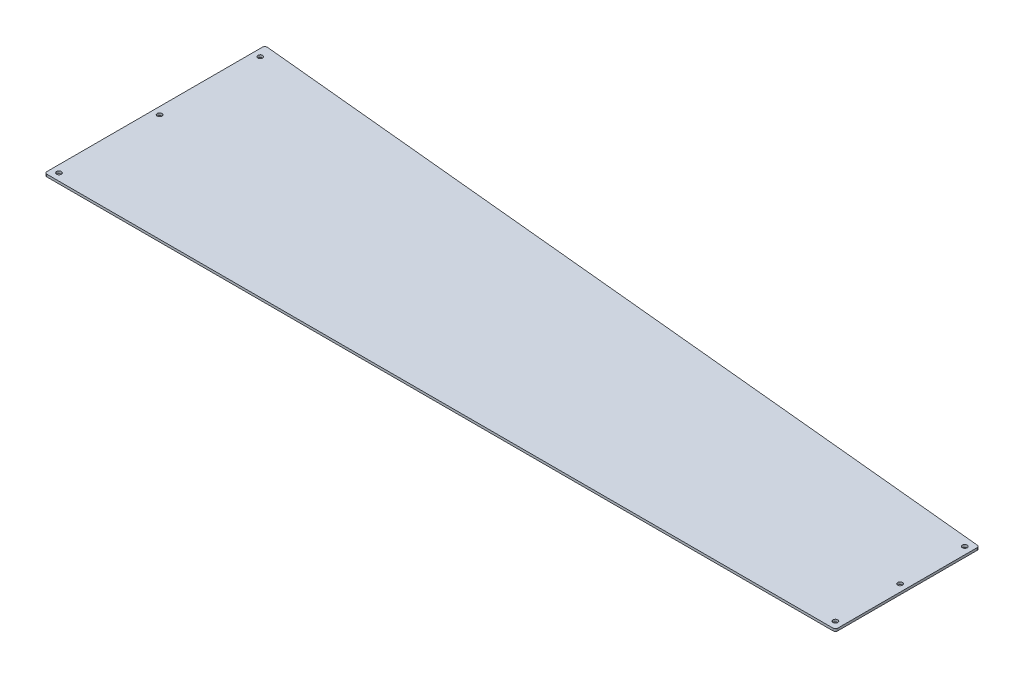
SolidWorks part; units mm, degrees
material "PC High Viscosity"
ref_plane "Front Plane" through (0, 0, 0) normal (0, 0, 1) x (1, 0, 0)
ref_plane "Top Plane" through (0, 0, 0) normal (0, 1, 0) x (1, 0, 0)
ref_plane "Right Plane" through (0, 0, 0) normal (1, 0, 0) x (0, 0, -1)
sketch "Sketch1" plane through (0, 0, 0) normal (0, 1, 0) x (1, 0, 0)
  line L0 (-634.1645, 176.7974) -> (413.5855, 75.1974)
  line L2 (-634.1645, 176.7974) -> (-634.1645, -115.3026)
  line L3 (-634.1645, -115.3026) -> (413.5855, -115.3026)
  line L4 (413.5855, 75.1974) -> (413.5855, -115.3026)
  line L5 (-634.1645, 176.7974) -> (413.5855, -115.3026) construction
  line L6 (-634.1645, -115.3026) -> (413.5855, 75.1974) construction
  point P0 (0, 0)
  dimension "D1" = 292.1
  dimension "D2" = 1047.75
  dimension "D3" = 190.5
extrude "Boss-Extrude1" add sketch "Sketch1" along normal blind 3.175
fillet "Fillet1" radius 3.175 4 edges at (413.5855, 1.5875, 115.3026) (413.5855, 1.5875, -75.1974) (-634.1645, 1.5875, 115.3026) (-634.1645, 1.5875, -176.7974)
hole_wizard "1/4 (0.25) Diameter Hole1" positions "Sketch2" profile "Sketch3" hole size "1/4" standard "ANSI Inch" end condition through all
sketch "Sketch2" plane through (0, 3.175, 0) normal (0, 1, 0) x (1, 0, 0)
  line L0 (413.5855, -112.1276) -> (413.5855, 72.3154) construction
  line L1 (-630.9895, -115.3026) -> (410.4105, -115.3026) construction
  line L2 (-634.1645, 173.2996) -> (-634.1645, -112.1276) construction
  point P0 (404.0605, 65.6724)
  point P2 (404.0605, -20.0526)
  point P4 (404.0605, -105.7776)
  point P11 (-624.6395, -105.7776)
  point P13 (-624.6395, 27.5724)
  point P15 (-624.6395, 160.9224)
  dimension "D1" = 85.725
  dimension "D2" = 85.725
  dimension "D3" = 9.525
  dimension "D4" = 9.525
  dimension "D5" = 133.35
  dimension "D6" = 133.35
  dimension "D7" = 9.525
sketch "Sketch3" plane through (404.0605, 3.175, -65.6724) normal (1, 0, 0) x (0, 0, 1)
  line L0 (0, 0) -> (0, 3.175)
  line L1 (0, 3.175) -> (3.175, 3.175)
  line L2 (3.175, 3.175) -> (3.175, 0)
  line L5 (3.175, 0) -> (0, 0)
  line L11 (0, -6.35) -> (0, 107.95) construction
  dimension "Thru Hole Dia." = 6.35
  dimension "Thru Hole Depth" = 3.175
equation "\"D2@Sketch2\"=\"D1@Sketch2\""
equation "\"D6@Sketch2\"=\"D5@Sketch2\""
